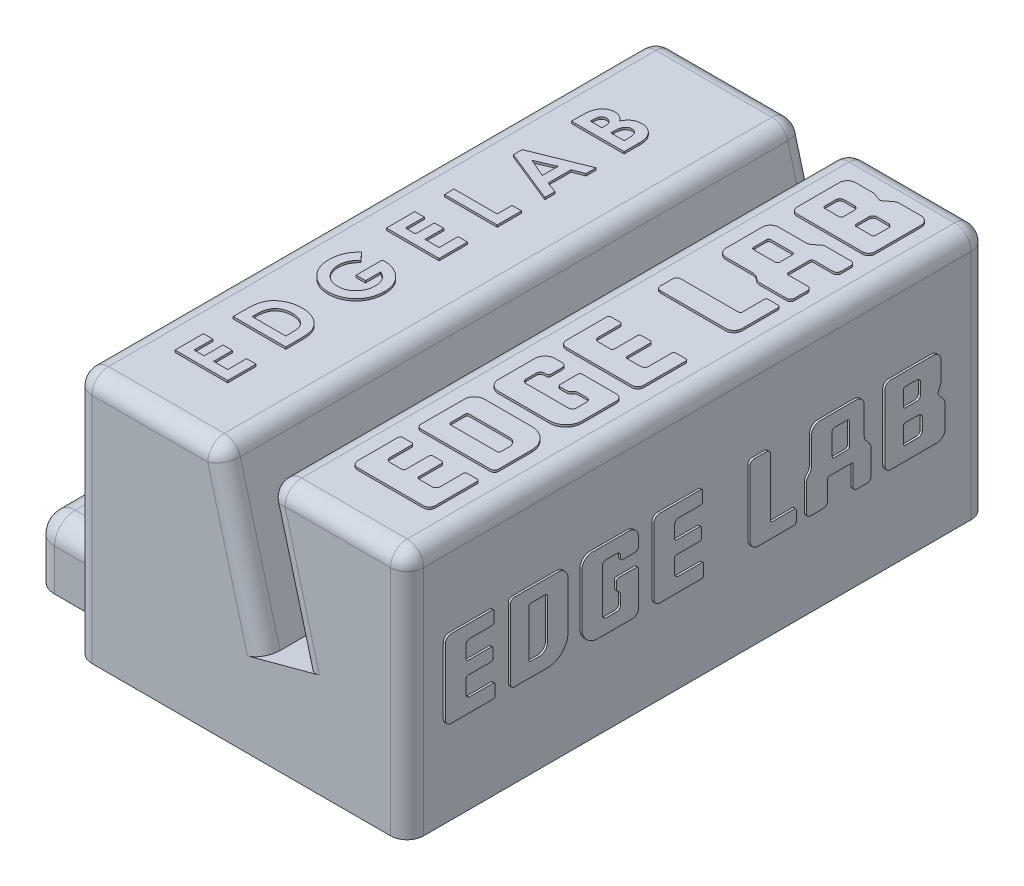
SolidWorks part; units mm, degrees
ref_plane "Front Plane" through (0, 0, 0) normal (0, 0, 1) x (1, 0, 0)
ref_plane "Top Plane" through (0, 0, 0) normal (0, 1, 0) x (1, 0, 0)
ref_plane "Right Plane" through (0, 0, 0) normal (1, 0, 0) x (0, 0, -1)
sketch "Sketch1" plane through (0, 0, 0) normal (0, 0, 1) x (1, 0, 0)
  line L0 (-5, 30) -> (5.3528, -8.637)
  line L1 (-40, -30) -> (40, -30)
  line L2 (-40, -30) -> (-40, 30)
  line L3 (-40, 30) -> (-5, 30)
  line L4 (40, -30) -> (40, 30)
  line L5 (-40, -30) -> (40, 30) construction
  line L6 (-40, 30) -> (40, -30) construction
  line L7 (5.3528, -8.637) -> (15.012, -6.0488)
  line L8 (15.012, -6.0488) -> (5.3528, 30)
  line L9 (5.3528, 30) -> (40, 30)
  point P0 (0, 0)
  dimension "D1" = 80
  dimension "D2" = 60
  dimension "D3" = 10
  dimension "D4" = 15
  dimension "D5" = 40
  dimension "D6" = 35
extrude "Boss-Extrude1" add sketch "Sketch1" along normal mid plane 140
fillet "Fillet1" radius 4 16 edges at (10.1824, 11.9756, 70) (0.1764, 10.6815, 70) (10.1824, 11.9756, -70) (0.1764, 10.6815, -70) (-40, 0, -70) (-40, 0, 70) (40, 0, 70) (40, 0, -70) (-22.5, 30, -70) (22.6764, 30, -70) (22.6764, 30, 70) (-22.5, 30, 70) (-40, 30, 0) (40, 30, 0) (5.3528, 30, 0) (-5, 30, 0)
sketch "Sketch2" plane through (0, 30, 0) normal (0, 1, 0) x (1, 0, 0)
  line L0 (-18.2056, -66) -> (-18.2056, 66) construction
  line L1 (-36, -66) -> (-8.0693, -66) construction
  line L2 (-4.2056, 66) -> (-4.2056, -66) construction
  line L3 (-8.0693, 66) -> (-36, 66) construction
  text T0 "<b>E D G E L A B </b>" font "Century Gothic" height in points 48
  dimension "D1" = 14
extrude "Boss-Extrude2" add sketch "Sketch2" along normal mid plane 1
sketch "Sketch3" plane through (40, 0, 0) normal (1, 0, 0) x (0, 0, -1)
  line L1 (-61.2851, 9.4066) -> (59.2413, 9.4066) construction
  line L2 (-61.2851, 9.4066) -> (-61.2851, -9.3242) construction
  line L3 (-61.2851, -9.3242) -> (59.2413, -9.3242) construction
  line L4 (59.2413, 9.4066) -> (59.2413, -9.3242) construction
  spline S0 degree 2 poles (49.1702, -1.7787) (49.1702, -3.634) (49.1702, -5.4894) (49.1702, -5.9794) (49.6602, -5.9794) (51.1939, -5.9794) (52.7277, -5.9794) (53.7077, -5.9794) (53.7077, -4.9994) knots -167.601718 -167.601718 -167.601718 -129.737239 -129.737239 -121.883257 -121.883257 -90.581831 -90.581831 -74.873868 -74.873868 -74.873868 weights 1 1 1 0.707107 1 1 1 0.707107 1
  spline S1 degree 2 poles (53.7077, -4.9994) (53.7077, -3.634) (53.7077, -2.2687) (53.7077, -1.2887) (52.7277, -1.2887) (51.1939, -1.2887) (49.6602, -1.2887) (49.1702, -1.2887) (49.1702, -1.7787) knots -250.329568 -250.329568 -250.329568 -222.465088 -222.465088 -206.757125 -206.757125 -175.4557 -175.4557 -167.601718 -167.601718 -167.601718 weights 1 1 1 0.707107 1 1 1 0.707107 1
  spline S2 degree 2 poles (53.3258, 2.7824) (53.3258, 4.0329) (53.3258, 5.2834) (53.3258, 6.2634) (52.3458, 6.2634) (51.003, 6.2634) (49.6602, 6.2634) (49.1702, 6.2634) (49.1702, 5.7734) knots 398.296758 398.296758 398.296758 423.817476 423.817476 439.525439 439.525439 466.92947 466.92947 474.783451 474.783451 474.783451 weights 1 1 1 0.707107 1 1 1 0.707107 1
  spline S3 degree 2 poles (49.1702, 5.7734) (49.1702, 4.0329) (49.1702, 2.2924) (49.1702, 1.8024) (49.6602, 1.8024) (51.003, 1.8024) (52.3458, 1.8024) (53.3258, 1.8024) (53.3258, 2.7824) knots 311.810065 311.810065 311.810065 347.330782 347.330782 355.184764 355.184764 382.588795 382.588795 398.296758 398.296758 398.296758 weights 1 1 1 0.707107 1 1 1 0.707107 1
  spline S4 degree 2 poles (44.6664, -7.8542) (44.6664, 0.0412) (44.6664, 7.9366) (44.6664, 9.4066) (46.1364, 9.4066) (51.2216, 9.4066) (56.3069, 9.4066) (58.2669, 9.4066) (58.2669, 7.4466) (58.2669, 5.3695) (58.2669, 3.2924) (58.2669, 2.9275) (58.1356, 2.5871) knots 461.80003 461.80003 461.80003 622.930523 622.930523 646.492467 646.492467 750.273029 750.273029 781.688955 781.688955 824.078534 824.078534 831.441149 831.441149 831.441149 weights 1 1 1 0.707107 1 1 1 0.707107 1 1 1 0.983108 1
  spline S5 degree 2 poles (58.1356, 2.5871) (57.8372, 1.8135) (57.5388, 1.04) (57.4394, 0.7821) (57.6086, 0.5636) (58.2197, -0.2255) (58.8308, -1.0145) (59.2413, -1.5444) (59.2413, -2.2147) (59.2413, -4.7894) (59.2413, -7.3642) (59.2413, -9.3242) (57.2813, -9.3242) (51.7088, -9.3242) (46.1364, -9.3242) (44.6664, -9.3242) (44.6664, -7.8542) knots 184.948682 184.948682 184.948682 201.869362 201.869362 207.005035 207.005035 227.373046 227.373046 240.553121 240.553121 293.098969 293.098969 324.514895 324.514895 438.238085 438.238085 461.80003 461.80003 461.80003 weights 1 1 1 0.870998 1 1 1 0.946204 1 1 1 0.707107 1 1 1 0.707107 1
  spline S6 degree 2 poles (35.651, 6.2634) (34.0595, 6.2634) (32.468, 6.2634) (31.978, 6.2634) (31.978, 5.7734) (31.978, 3.1282) (31.978, 0.483) (31.978, -0.007) (32.468, -0.007) knots -236.822202 -236.822202 -236.822202 -204.342778 -204.342778 -196.488797 -196.488797 -142.504795 -142.504795 -134.650813 -134.650813 -134.650813 weights 1 1 1 0.707107 1 1 1 0.707107 1
  spline S7 degree 2 poles (32.468, -0.007) (34.0595, -0.007) (35.651, -0.007) (36.141, -0.007) (36.141, 0.483) (36.141, 3.1282) (36.141, 5.7734) (36.141, 6.2634) (35.651, 6.2634) knots -338.993592 -338.993592 -338.993592 -306.514167 -306.514167 -298.660186 -298.660186 -244.676184 -244.676184 -236.822202 -236.822202 -236.822202 weights 1 1 1 0.707107 1 1 1 0.707107 1
  spline S8 degree 2 poles (39.7047, 7.4466) (39.7047, 9.4066) (37.7447, 9.4066) (33.3708, 9.4066) (28.9969, 9.4066) (27.0369, 9.4066) (27.0369, 7.4466) (27.0369, 4.1917) (27.0369, 0.9368) (27.0369, 0.2291) (26.5848, -0.3154) (26.4181, -0.5161) (26.2514, -0.7168) (25.7993, -1.2612) (25.7993, -1.9689) (25.7993, -5.1566) (25.7993, -8.3442) (25.7993, -9.3242) (26.7793, -9.3242) (28.3348, -9.3242) (29.8903, -9.3242) knots 400.035539 400.035539 400.035539 431.451465 431.451465 520.714602 520.714602 552.130529 552.130529 618.557077 618.557077 632.417382 632.417382 637.741813 637.741813 651.602118 651.602118 716.655463 716.655463 732.363426 732.363426 764.108188 764.108188 764.108188 weights 1 0.707107 1 1 1 0.707107 1 1 1 0.940565 1 1 1 0.940565 1 1 1 0.707107 1 1 1
  spline S9 degree 2 poles (29.8903, -9.3242) (30.8703, -9.3242) (30.8703, -8.3442) (30.8703, -6.04) (30.8703, -3.7358) (30.8703, -3.2458) (31.3603, -3.2458) (33.9435, -3.2458) (36.5268, -3.2458) (37.0168, -3.2458) (37.0168, -3.7358) (37.0168, -6.04) (37.0168, -8.3442) (37.0168, -9.3242) (37.9968, -9.3242) (39.1851, -9.3242) (40.3734, -9.3242) (41.3534, -9.3242) (41.3534, -8.3442) (41.3534, -5.3156) (41.3534, -2.2871) (41.3534, -1.7563) (41.0143, -1.348) (40.5856, -0.8317) (40.1568, -0.3154) (39.7047, 0.2291) (39.7047, 0.9368) (39.7047, 4.1917) (39.7047, 7.4466) knots 0 0 0 15.707963 15.707963 62.731742 62.731742 70.585723 70.585723 123.304654 123.304654 131.158636 131.158636 178.182414 178.182414 193.890378 193.890378 218.142207 218.142207 233.85017 233.85017 295.657088 295.657088 306.052316 306.052316 319.748686 319.748686 333.608991 333.608991 400.035539 400.035539 400.035539 weights 1 0.707107 1 1 1 0.707107 1 1 1 0.707107 1 1 1 0.707107 1 1 1 0.707107 1 1 1 0.940565 1 1 1 0.940565 1 1 1
  spline S10 degree 2 poles (23.354, -8.8342) (23.354, -9.3242) (22.864, -9.3242) (18.4989, -9.3242) (14.1338, -9.3242) (12.1738, -9.3242) (12.1738, -7.3642) (12.1738, 0.5312) (12.1738, 8.4266) knots 297.338 297.338 297.338 305.191981 305.191981 394.275598 394.275598 425.691525 425.691525 586.822018 586.822018 586.822018 weights 1 0.707107 1 1 1 0.707107 1 1 1
  spline S11 degree 2 poles (12.1738, 8.4266) (12.1738, 9.4066) (13.1538, 9.4066) (14.6443, 9.4066) (16.1349, 9.4066) (17.1149, 9.4066) (17.1149, 8.4266) (17.1149, 1.4982) (17.1149, -5.4302) (17.1149, -5.9202) (17.6049, -5.9202) (20.2344, -5.9202) (22.864, -5.9202) (23.354, -5.9202) (23.354, -6.4102) (23.354, -7.6222) (23.354, -8.8342) knots 0 0 0 15.707963 15.707963 46.127608 46.127608 61.835571 61.835571 203.231548 203.231548 211.085529 211.085529 264.749502 264.749502 272.603484 272.603484 297.338 297.338 297.338 weights 1 0.707107 1 1 1 0.707107 1 1 1 0.707107 1 1 1 0.707107 1 1 1
  spline S12 degree 2 poles (-19.5122, 0.9279) (-20.0022, 0.9279) (-20.0022, 0.4379) (-20.0022, -0.3545) (-20.0022, -1.1469) (-20.0022, -1.6264) (-19.6237, -1.9206) (-19.501, -2.016) (-19.3784, -2.1114) (-18.9998, -2.4056) (-18.9998, -2.8851) (-18.9998, -3.9327) (-18.9998, -4.9803) (-18.9998, -5.9603) (-19.9798, -5.9603) (-21.2079, -5.9603) (-22.436, -5.9603) (-23.416, -5.9603) (-23.416, -4.9803) (-23.416, 0.1062) (-23.416, 5.1926) (-23.416, 6.1726) (-22.436, 6.1726) (-21.2079, 6.1726) (-19.9798, 6.1726) (-18.9998, 6.1726) (-18.9998, 5.1926) (-18.9998, 4.9395) (-18.9998, 4.6865) (-18.9998, 4.1965) (-18.5098, 4.1965) (-17.0861, 4.1965) (-15.6623, 4.1965) (-14.6823, 4.1965) (-14.6823, 5.1765) (-14.6823, 6.0665) (-14.6823, 6.9566) (-14.6823, 9.4066) (-17.1323, 9.4066) (-20.2742, 9.4066) (-23.416, 9.4066) knots 562.622876 562.622876 562.622876 570.476858 570.476858 586.648376 586.648376 595.748248 595.748248 598.919425 598.919425 608.019297 608.019297 629.399219 629.399219 645.107182 645.107182 670.169937 670.169937 685.8779 685.8779 789.683176 789.683176 805.391139 805.391139 830.453894 830.453894 846.161857 846.161857 851.326609 851.326609 859.180591 859.180591 888.236751 888.236751 903.944714 903.944714 922.109466 922.109466 961.379374 961.379374 1025.498289 1025.498289 1025.498289 weights 1 0.707107 1 1 1 0.898264 1 1 1 0.898264 1 1 1 0.707107 1 1 1 0.707107 1 1 1 0.707107 1 1 1 0.707107 1 1 1 0.707107 1 1 1 0.707107 1 1 1 0.707107 1 1 1
  spline S13 degree 2 poles (-23.416, 9.4066) (-24.6615, 9.4066) (-25.9071, 9.4066) (-28.3571, 9.4066) (-28.3571, 6.9566) (-28.3571, 0.7762) (-28.3571, -5.4042) (-28.3571, -9.3242) (-24.4371, -9.3242) (-20.2947, -9.3242) (-16.1523, -9.3242) (-14.6823, -9.3242) (-14.6823, -7.8542) (-14.6823, -3.7081) (-14.6823, 0.4379) (-14.6823, 0.9279) (-15.1723, 0.9279) (-17.3423, 0.9279) (-19.5122, 0.9279) knots 64.118914 64.118914 64.118914 89.538559 89.538559 128.808467 128.808467 254.93896 254.93896 317.770813 317.770813 402.309372 402.309372 425.871317 425.871317 510.484221 510.484221 518.338202 518.338202 562.622876 562.622876 562.622876 weights 1 1 1 0.707107 1 1 1 0.707107 1 1 1 0.707107 1 1 1 0.707107 1 1 1
  spline S14 degree 2 poles (-40.6388, 6.1726) (-38.8795, 6.1726) (-37.1203, 6.1726) (-36.6303, 6.1726) (-36.6303, 5.6826) (-36.6303, 0.8418) (-36.6303, -3.9991) (-36.6303, -5.9567) (-38.5879, -5.9591) knots -217.757092 -217.757092 -217.757092 -181.853982 -181.853982 -174 -174 -75.207429 -75.207429 -43.815822 -43.815822 -43.815822 weights 1 1 1 0.707107 1 1 1 0.707537 1
  spline S15 degree 2 poles (-38.5879, -5.9591) (-39.6131, -5.9603) (-40.6382, -5.9615) (-40.8413, -5.9618) (-40.9851, -5.8182) (-41.1288, -5.6747) (-41.1288, -5.4715) (-41.1288, 0.1055) (-41.1288, 5.6826) (-41.1288, 6.1726) (-40.6388, 6.1726) knots -368.210498 -368.210498 -368.210498 -347.289133 -347.289133 -343.359103 -343.359103 -339.429072 -339.429072 -225.611074 -225.611074 -217.757092 -217.757092 -217.757092 weights 1 1 1 0.923763 1 0.923763 1 1 1 0.707107 1
  spline S16 degree 2 poles (-36.5892, -9.3242) (-31.6892, -9.3242) (-31.6892, -4.4242) (-31.6892, 1.2662) (-31.6892, 6.9566) (-31.6892, 9.4066) (-34.1392, 9.4066) (-39.3695, 9.4066) (-44.5999, 9.4066) knots 284.288819 284.288819 284.288819 362.828635 362.828635 478.959128 478.959128 518.229036 518.229036 624.971435 624.971435 624.971435 weights 1 0.707107 1 1 1 0.707107 1 1 1
  spline S17 degree 2 poles (-44.5999, 9.4066) (-45.5799, 9.4066) (-45.5799, 8.4266) (-45.5799, 0.0412) (-45.5799, -8.3442) (-45.5799, -9.3242) (-44.5999, -9.3242) (-40.5945, -9.3242) (-36.5892, -9.3242) knots 0 0 0 15.707963 15.707963 186.838456 186.838456 202.546419 202.546419 284.288819 284.288819 284.288819 weights 1 0.707107 1 1 1 0.707107 1 1 1
  spline S82 degree 2 poles (-61.2851, 7.9366) (-61.2851, 0.0412) (-61.2851, -7.8542) (-61.2851, -9.3242) (-59.8151, -9.3242) (-54.7806, -9.3242) (-49.7461, -9.3242) (-49.2561, -9.3242) (-49.2561, -8.8342) (-49.2561, -7.6518) (-49.2561, -6.4694) (-49.2561, -5.9794) (-49.7461, -5.9794) (-52.5266, -5.9794) (-55.3071, -5.9794) (-56.2871, -5.9794) (-56.2871, -4.9994) (-56.2871, -3.389) (-56.2871, -1.7787) (-56.2871, -1.2887) (-55.7971, -1.2887) knots 475.999021 475.999021 475.999021 637.129514 637.129514 660.691459 660.691459 763.436857 763.436857 771.290839 771.290839 795.421332 795.421332 803.275313 803.275313 860.020712 860.020712 875.728675 875.728675 908.593155 908.593155 916.447135 916.447135 916.447135 weights 1 1 1 0.707107 1 1 1 0.707107 1 1 1 0.707107 1 1 1 0.707107 1 1 1 0.707107 1
  spline S83 degree 2 poles (-55.7971, -1.2887) (-53.0207, -1.2887) (-50.2443, -1.2887) (-49.7543, -1.2887) (-49.7543, -0.7987) (-49.7543, 0.2569) (-49.7543, 1.3124) (-49.7543, 1.8024) (-50.2443, 1.8024) (-53.0207, 1.8024) (-55.7971, 1.8024) (-56.2871, 1.8024) (-56.2871, 2.2924) (-56.2871, 3.7425) (-56.2871, 5.1926) (-56.2871, 6.1726) (-55.3071, 6.1726) (-52.6611, 6.1726) (-50.0151, 6.1726) (-49.5251, 6.1726) (-49.5251, 6.6626) (-49.5251, 7.7896) (-49.5251, 8.9166) (-49.5251, 9.4066) (-50.0151, 9.4066) (-54.9151, 9.4066) (-59.8151, 9.4066) (-61.2851, 9.4066) (-61.2851, 7.9366) knots 55.999999 55.999999 55.999999 112.661842 112.661842 120.515824 120.515824 142.057243 142.057243 149.911225 149.911225 206.573067 206.573067 214.427049 214.427049 244.02115 244.02115 259.729113 259.729113 313.729113 313.729113 321.583095 321.583095 344.583095 344.583095 352.437076 352.437076 452.437076 452.437076 475.999021 475.999021 475.999021 weights 1 1 1 0.707107 1 1 1 0.707107 1 1 1 0.707107 1 1 1 0.707107 1 1 1 0.707107 1 1 1 0.707107 1 1 1 0.707107 1
  spline S84 degree 2 poles (-11.0111, 7.9366) (-11.0111, 0.0412) (-11.0111, -7.8542) (-11.0111, -9.3242) (-9.5411, -9.3242) (-4.5066, -9.3242) (0.5279, -9.3242) (1.0179, -9.3242) (1.0179, -8.8342) (1.0179, -7.6518) (1.0179, -6.4694) (1.0179, -5.9794) (0.5279, -5.9794) (-2.2526, -5.9794) (-5.0331, -5.9794) (-6.0131, -5.9794) (-6.0131, -4.9994) (-6.0131, -3.389) (-6.0131, -1.7787) (-6.0131, -1.2887) (-5.5231, -1.2887) knots 475.999021 475.999021 475.999021 637.129514 637.129514 660.691459 660.691459 763.436857 763.436857 771.290839 771.290839 795.421332 795.421332 803.275313 803.275313 860.020712 860.020712 875.728675 875.728675 908.593155 908.593155 916.447135 916.447135 916.447135 weights 1 1 1 0.707107 1 1 1 0.707107 1 1 1 0.707107 1 1 1 0.707107 1 1 1 0.707107 1
  spline S85 degree 2 poles (-5.5231, -1.2887) (-2.7467, -1.2887) (0.0297, -1.2887) (0.5197, -1.2887) (0.5197, -0.7987) (0.5197, 0.2569) (0.5197, 1.3124) (0.5197, 1.8024) (0.0297, 1.8024) (-2.7467, 1.8024) (-5.5231, 1.8024) (-6.0131, 1.8024) (-6.0131, 2.2924) (-6.0131, 3.7425) (-6.0131, 5.1926) (-6.0131, 6.1726) (-5.0331, 6.1726) (-2.3871, 6.1726) (0.2589, 6.1726) (0.7489, 6.1726) (0.7489, 6.6626) (0.7489, 7.7896) (0.7489, 8.9166) (0.7489, 9.4066) (0.2589, 9.4066) (-4.6411, 9.4066) (-9.5411, 9.4066) (-11.0111, 9.4066) (-11.0111, 7.9366) knots 55.999999 55.999999 55.999999 112.661842 112.661842 120.515824 120.515824 142.057243 142.057243 149.911225 149.911225 206.573067 206.573067 214.427049 214.427049 244.02115 244.02115 259.729113 259.729113 313.729113 313.729113 321.583095 321.583095 344.583095 344.583095 352.437076 352.437076 452.437076 452.437076 475.999021 475.999021 475.999021 weights 1 1 1 0.707107 1 1 1 0.707107 1 1 1 0.707107 1 1 1 0.707107 1 1 1 0.707107 1 1 1 0.707107 1 1 1 0.707107 1
extrude "Boss-Extrude3" add sketch "Sketch3" along normal mid plane 1
sketch "Sketch4" plane through (0, 30, 0) normal (0, 1, 0) x (1, 0, 0)
  line L1 (14.2135, -57.5951) -> (14.2135, 62.9313) construction
  line L2 (14.2135, -57.5951) -> (32.9443, -57.5951) construction
  line L3 (32.9443, -57.5951) -> (32.9443, 62.9313) construction
  line L4 (14.2135, 62.9313) -> (32.9443, 62.9313) construction
  spline S0 degree 2 poles (25.3988, 52.8602) (27.2541, 52.8602) (29.1095, 52.8602) (29.5995, 52.8602) (29.5995, 53.3502) (29.5995, 54.8839) (29.5995, 56.4177) (29.5995, 57.3977) (28.6195, 57.3977) knots -167.601718 -167.601718 -167.601718 -129.737239 -129.737239 -121.883257 -121.883257 -90.581831 -90.581831 -74.873868 -74.873868 -74.873868 weights 1 1 1 0.707107 1 1 1 0.707107 1
  spline S1 degree 2 poles (28.6195, 57.3977) (27.2541, 57.3977) (25.8888, 57.3977) (24.9088, 57.3977) (24.9088, 56.4177) (24.9088, 54.8839) (24.9088, 53.3502) (24.9088, 52.8602) (25.3988, 52.8602) knots -250.329568 -250.329568 -250.329568 -222.465088 -222.465088 -206.757125 -206.757125 -175.4557 -175.4557 -167.601718 -167.601718 -167.601718 weights 1 1 1 0.707107 1 1 1 0.707107 1
  spline S2 degree 2 poles (20.8377, 57.0158) (19.5872, 57.0158) (18.3367, 57.0158) (17.3567, 57.0158) (17.3567, 56.0358) (17.3567, 54.693) (17.3567, 53.3502) (17.3567, 52.8602) (17.8467, 52.8602) knots 398.296758 398.296758 398.296758 423.817476 423.817476 439.525439 439.525439 466.92947 466.92947 474.783451 474.783451 474.783451 weights 1 1 1 0.707107 1 1 1 0.707107 1
  spline S3 degree 2 poles (17.8467, 52.8602) (19.5872, 52.8602) (21.3277, 52.8602) (21.8177, 52.8602) (21.8177, 53.3502) (21.8177, 54.693) (21.8177, 56.0358) (21.8177, 57.0158) (20.8377, 57.0158) knots 311.810065 311.810065 311.810065 347.330782 347.330782 355.184764 355.184764 382.588795 382.588795 398.296758 398.296758 398.296758 weights 1 1 1 0.707107 1 1 1 0.707107 1
  spline S4 degree 2 poles (31.4743, 48.3564) (23.5789, 48.3564) (15.6835, 48.3564) (14.2135, 48.3564) (14.2135, 49.8264) (14.2135, 54.9116) (14.2135, 59.9969) (14.2135, 61.9569) (16.1735, 61.9569) (18.2506, 61.9569) (20.3277, 61.9569) (20.6926, 61.9569) (21.033, 61.8256) knots 461.80003 461.80003 461.80003 622.930523 622.930523 646.492467 646.492467 750.273029 750.273029 781.688955 781.688955 824.078534 824.078534 831.441149 831.441149 831.441149 weights 1 1 1 0.707107 1 1 1 0.707107 1 1 1 0.983108 1
  spline S5 degree 2 poles (21.033, 61.8256) (21.8066, 61.5272) (22.5801, 61.2288) (22.838, 61.1293) (23.0565, 61.2986) (23.8456, 61.9097) (24.6346, 62.5208) (25.1645, 62.9313) (25.8348, 62.9313) (28.4095, 62.9313) (30.9843, 62.9313) (32.9443, 62.9313) (32.9443, 60.9713) (32.9443, 55.3988) (32.9443, 49.8264) (32.9443, 48.3564) (31.4743, 48.3564) knots 184.948682 184.948682 184.948682 201.869362 201.869362 207.005035 207.005035 227.373046 227.373046 240.553121 240.553121 293.098969 293.098969 324.514895 324.514895 438.238085 438.238085 461.80003 461.80003 461.80003 weights 1 1 1 0.870998 1 1 1 0.946204 1 1 1 0.707107 1 1 1 0.707107 1
  spline S6 degree 2 poles (17.3567, 39.341) (17.3567, 37.7495) (17.3567, 36.158) (17.3567, 35.668) (17.8467, 35.668) (20.4919, 35.668) (23.1371, 35.668) (23.6271, 35.668) (23.6271, 36.158) knots -236.822202 -236.822202 -236.822202 -204.342778 -204.342778 -196.488797 -196.488797 -142.504795 -142.504795 -134.650813 -134.650813 -134.650813 weights 1 1 1 0.707107 1 1 1 0.707107 1
  spline S7 degree 2 poles (23.6271, 36.158) (23.6271, 37.7495) (23.6271, 39.341) (23.6271, 39.831) (23.1371, 39.831) (20.4919, 39.831) (17.8467, 39.831) (17.3567, 39.831) (17.3567, 39.341) knots -338.993592 -338.993592 -338.993592 -306.514167 -306.514167 -298.660186 -298.660186 -244.676184 -244.676184 -236.822202 -236.822202 -236.822202 weights 1 1 1 0.707107 1 1 1 0.707107 1
  spline S8 degree 2 poles (16.1735, 43.3947) (14.2135, 43.3947) (14.2135, 41.4347) (14.2135, 37.0608) (14.2135, 32.6869) (14.2135, 30.7269) (16.1735, 30.7269) (19.4284, 30.7269) (22.6833, 30.7269) (23.391, 30.7269) (23.9354, 30.2748) (24.1362, 30.1081) (24.3369, 29.9414) (24.8813, 29.4893) (25.589, 29.4893) (28.7766, 29.4893) (31.9643, 29.4893) (32.9443, 29.4893) (32.9443, 30.4693) (32.9443, 32.0248) (32.9443, 33.5803) knots 400.035539 400.035539 400.035539 431.451465 431.451465 520.714602 520.714602 552.130529 552.130529 618.557077 618.557077 632.417382 632.417382 637.741813 637.741813 651.602118 651.602118 716.655463 716.655463 732.363426 732.363426 764.108188 764.108188 764.108188 weights 1 0.707107 1 1 1 0.707107 1 1 1 0.940565 1 1 1 0.940565 1 1 1 0.707107 1 1 1
  spline S9 degree 2 poles (32.9443, 33.5803) (32.9443, 34.5603) (31.9643, 34.5603) (29.6601, 34.5603) (27.3559, 34.5603) (26.8659, 34.5603) (26.8659, 35.0503) (26.8659, 37.6335) (26.8659, 40.2167) (26.8659, 40.7067) (27.3559, 40.7067) (29.6601, 40.7067) (31.9643, 40.7067) (32.9443, 40.7067) (32.9443, 41.6867) (32.9443, 42.8751) (32.9443, 44.0634) (32.9443, 45.0434) (31.9643, 45.0434) (28.9357, 45.0434) (25.9072, 45.0434) (25.3764, 45.0434) (24.9681, 44.7043) (24.4517, 44.2756) (23.9354, 43.8468) (23.391, 43.3947) (22.6833, 43.3947) (19.4284, 43.3947) (16.1735, 43.3947) knots 0 0 0 15.707963 15.707963 62.731742 62.731742 70.585723 70.585723 123.304654 123.304654 131.158636 131.158636 178.182414 178.182414 193.890378 193.890378 218.142207 218.142207 233.85017 233.85017 295.657088 295.657088 306.052316 306.052316 319.748686 319.748686 333.608991 333.608991 400.035539 400.035539 400.035539 weights 1 0.707107 1 1 1 0.707107 1 1 1 0.707107 1 1 1 0.707107 1 1 1 0.707107 1 1 1 0.940565 1 1 1 0.940565 1 1 1
  spline S10 degree 2 poles (32.4543, 27.0439) (32.9443, 27.0439) (32.9443, 26.5539) (32.9443, 22.1888) (32.9443, 17.8238) (32.9443, 15.8638) (30.9843, 15.8638) (23.0889, 15.8638) (15.1935, 15.8638) knots 297.338 297.338 297.338 305.191981 305.191981 394.275598 394.275598 425.691525 425.691525 586.822018 586.822018 586.822018 weights 1 0.707107 1 1 1 0.707107 1 1 1
  spline S11 degree 2 poles (15.1935, 15.8638) (14.2135, 15.8638) (14.2135, 16.8438) (14.2135, 18.3343) (14.2135, 19.8249) (14.2135, 20.8049) (15.1935, 20.8049) (22.1219, 20.8049) (29.0503, 20.8049) (29.5403, 20.8049) (29.5403, 21.2949) (29.5403, 23.9244) (29.5403, 26.5539) (29.5403, 27.0439) (30.0303, 27.0439) (31.2423, 27.0439) (32.4543, 27.0439) knots 0 0 0 15.707963 15.707963 46.127608 46.127608 61.835571 61.835571 203.231548 203.231548 211.085529 211.085529 264.749502 264.749502 272.603484 272.603484 297.338 297.338 297.338 weights 1 0.707107 1 1 1 0.707107 1 1 1 0.707107 1 1 1 0.707107 1 1 1
  spline S12 degree 2 poles (22.6922, -15.8222) (22.6922, -16.3122) (23.1822, -16.3122) (23.9746, -16.3122) (24.767, -16.3122) (25.2464, -16.3122) (25.5407, -15.9337) (25.6361, -15.811) (25.7315, -15.6884) (26.0257, -15.3098) (26.5052, -15.3098) (27.5528, -15.3098) (28.6004, -15.3098) (29.5804, -15.3098) (29.5804, -16.2898) (29.5804, -17.5179) (29.5804, -18.746) (29.5804, -19.726) (28.6004, -19.726) (23.5139, -19.726) (18.4275, -19.726) (17.4475, -19.726) (17.4475, -18.746) (17.4475, -17.5179) (17.4475, -16.2898) (17.4475, -15.3098) (18.4275, -15.3098) (18.6805, -15.3098) (18.9336, -15.3098) (19.4236, -15.3098) (19.4236, -14.8198) (19.4236, -13.3961) (19.4236, -11.9723) (19.4236, -10.9923) (18.4436, -10.9923) (17.5535, -10.9923) (16.6635, -10.9923) (14.2135, -10.9923) (14.2135, -13.4423) (14.2135, -16.5842) (14.2135, -19.726) knots 562.622876 562.622876 562.622876 570.476858 570.476858 586.648376 586.648376 595.748248 595.748248 598.919425 598.919425 608.019297 608.019297 629.399219 629.399219 645.107182 645.107182 670.169937 670.169937 685.8779 685.8779 789.683176 789.683176 805.391139 805.391139 830.453894 830.453894 846.161857 846.161857 851.326609 851.326609 859.180591 859.180591 888.236751 888.236751 903.944714 903.944714 922.109466 922.109466 961.379374 961.379374 1025.498289 1025.498289 1025.498289 weights 1 0.707107 1 1 1 0.898264 1 1 1 0.898264 1 1 1 0.707107 1 1 1 0.707107 1 1 1 0.707107 1 1 1 0.707107 1 1 1 0.707107 1 1 1 0.707107 1 1 1 0.707107 1 1 1
  spline S13 degree 2 poles (14.2135, -19.726) (14.2135, -20.9716) (14.2135, -22.2171) (14.2135, -24.6671) (16.6635, -24.6671) (22.8439, -24.6671) (29.0243, -24.6671) (32.9443, -24.6671) (32.9443, -20.7471) (32.9443, -16.6047) (32.9443, -12.4623) (32.9443, -10.9923) (31.4743, -10.9923) (27.3282, -10.9923) (23.1822, -10.9923) (22.6922, -10.9923) (22.6922, -11.4823) (22.6922, -13.6523) (22.6922, -15.8222) knots 64.118914 64.118914 64.118914 89.538559 89.538559 128.808467 128.808467 254.93896 254.93896 317.770813 317.770813 402.309372 402.309372 425.871317 425.871317 510.484221 510.484221 518.338202 518.338202 562.622876 562.622876 562.622876 weights 1 1 1 0.707107 1 1 1 0.707107 1 1 1 0.707107 1 1 1 0.707107 1 1 1
  spline S14 degree 2 poles (17.4475, -36.9488) (17.4475, -35.1896) (17.4475, -33.4303) (17.4475, -32.9403) (17.9375, -32.9403) (22.7783, -32.9403) (27.6191, -32.9403) (29.5768, -32.9403) (29.5791, -34.8979) knots -217.757092 -217.757092 -217.757092 -181.853982 -181.853982 -174 -174 -75.207429 -75.207429 -43.815822 -43.815822 -43.815822 weights 1 1 1 0.707107 1 1 1 0.707537 1
  spline S15 degree 2 poles (29.5791, -34.8979) (29.5804, -35.9231) (29.5816, -36.9482) (29.5819, -37.1513) (29.4383, -37.2951) (29.2948, -37.4388) (29.0916, -37.4388) (23.5146, -37.4388) (17.9375, -37.4388) (17.4475, -37.4388) (17.4475, -36.9488) knots -368.210498 -368.210498 -368.210498 -347.289133 -347.289133 -343.359103 -343.359103 -339.429072 -339.429072 -225.611074 -225.611074 -217.757092 -217.757092 -217.757092 weights 1 1 1 0.923763 1 0.923763 1 1 1 0.707107 1
  spline S16 degree 2 poles (32.9443, -32.8992) (32.9443, -27.9992) (28.0443, -27.9992) (22.3539, -27.9992) (16.6635, -27.9992) (14.2135, -27.9992) (14.2135, -30.4492) (14.2135, -35.6796) (14.2135, -40.9099) knots 284.288819 284.288819 284.288819 362.828635 362.828635 478.959128 478.959128 518.229036 518.229036 624.971435 624.971435 624.971435 weights 1 0.707107 1 1 1 0.707107 1 1 1
  spline S17 degree 2 poles (14.2135, -40.9099) (14.2135, -41.8899) (15.1935, -41.8899) (23.5789, -41.8899) (31.9643, -41.8899) (32.9443, -41.8899) (32.9443, -40.9099) (32.9443, -36.9046) (32.9443, -32.8992) knots 0 0 0 15.707963 15.707963 186.838456 186.838456 202.546419 202.546419 284.288819 284.288819 284.288819 weights 1 0.707107 1 1 1 0.707107 1 1 1
  spline S82 degree 2 poles (15.6835, -57.5951) (23.5789, -57.5951) (31.4743, -57.5951) (32.9443, -57.5951) (32.9443, -56.1251) (32.9443, -51.0906) (32.9443, -46.0561) (32.9443, -45.5661) (32.4543, -45.5661) (31.2719, -45.5661) (30.0895, -45.5661) (29.5995, -45.5661) (29.5995, -46.0561) (29.5995, -48.8366) (29.5995, -51.6171) (29.5995, -52.5971) (28.6195, -52.5971) (27.0091, -52.5971) (25.3988, -52.5971) (24.9088, -52.5971) (24.9088, -52.1071) knots 475.999021 475.999021 475.999021 637.129514 637.129514 660.691459 660.691459 763.436857 763.436857 771.290839 771.290839 795.421332 795.421332 803.275313 803.275313 860.020712 860.020712 875.728675 875.728675 908.593155 908.593155 916.447135 916.447135 916.447135 weights 1 1 1 0.707107 1 1 1 0.707107 1 1 1 0.707107 1 1 1 0.707107 1 1 1 0.707107 1
  spline S83 degree 2 poles (24.9088, -52.1071) (24.9088, -49.3307) (24.9088, -46.5543) (24.9088, -46.0643) (24.4188, -46.0643) (23.3632, -46.0643) (22.3077, -46.0643) (21.8177, -46.0643) (21.8177, -46.5543) (21.8177, -49.3307) (21.8177, -52.1071) (21.8177, -52.5971) (21.3277, -52.5971) (19.8776, -52.5971) (18.4275, -52.5971) (17.4475, -52.5971) (17.4475, -51.6171) (17.4475, -48.9711) (17.4475, -46.3251) (17.4475, -45.8351) (16.9575, -45.8351) (15.8305, -45.8351) (14.7035, -45.8351) (14.2135, -45.8351) (14.2135, -46.3251) (14.2135, -51.2251) (14.2135, -56.1251) (14.2135, -57.5951) (15.6835, -57.5951) knots 55.999999 55.999999 55.999999 112.661842 112.661842 120.515824 120.515824 142.057243 142.057243 149.911225 149.911225 206.573067 206.573067 214.427049 214.427049 244.02115 244.02115 259.729113 259.729113 313.729113 313.729113 321.583095 321.583095 344.583095 344.583095 352.437076 352.437076 452.437076 452.437076 475.999021 475.999021 475.999021 weights 1 1 1 0.707107 1 1 1 0.707107 1 1 1 0.707107 1 1 1 0.707107 1 1 1 0.707107 1 1 1 0.707107 1 1 1 0.707107 1
  spline S84 degree 2 poles (15.6835, -7.3211) (23.5789, -7.3211) (31.4743, -7.3211) (32.9443, -7.3211) (32.9443, -5.8511) (32.9443, -0.8166) (32.9443, 4.2179) (32.9443, 4.7079) (32.4543, 4.7079) (31.2719, 4.7079) (30.0895, 4.7079) (29.5995, 4.7079) (29.5995, 4.2179) (29.5995, 1.4374) (29.5995, -1.3431) (29.5995, -2.3231) (28.6195, -2.3231) (27.0091, -2.3231) (25.3988, -2.3231) (24.9088, -2.3231) (24.9088, -1.8331) knots 475.999021 475.999021 475.999021 637.129514 637.129514 660.691459 660.691459 763.436857 763.436857 771.290839 771.290839 795.421332 795.421332 803.275313 803.275313 860.020712 860.020712 875.728675 875.728675 908.593155 908.593155 916.447135 916.447135 916.447135 weights 1 1 1 0.707107 1 1 1 0.707107 1 1 1 0.707107 1 1 1 0.707107 1 1 1 0.707107 1
  spline S85 degree 2 poles (24.9088, -1.8331) (24.9088, 0.9433) (24.9088, 3.7197) (24.9088, 4.2097) (24.4188, 4.2097) (23.3632, 4.2097) (22.3077, 4.2097) (21.8177, 4.2097) (21.8177, 3.7197) (21.8177, 0.9433) (21.8177, -1.8331) (21.8177, -2.3231) (21.3277, -2.3231) (19.8776, -2.3231) (18.4275, -2.3231) (17.4475, -2.3231) (17.4475, -1.3431) (17.4475, 1.3029) (17.4475, 3.9489) (17.4475, 4.4389) (16.9575, 4.4389) (15.8305, 4.4389) (14.7035, 4.4389) (14.2135, 4.4389) (14.2135, 3.9489) (14.2135, -0.9511) (14.2135, -5.8511) (14.2135, -7.3211) (15.6835, -7.3211) knots 55.999999 55.999999 55.999999 112.661842 112.661842 120.515824 120.515824 142.057243 142.057243 149.911225 149.911225 206.573067 206.573067 214.427049 214.427049 244.02115 244.02115 259.729113 259.729113 313.729113 313.729113 321.583095 321.583095 344.583095 344.583095 352.437076 352.437076 452.437076 452.437076 475.999021 475.999021 475.999021 weights 1 1 1 0.707107 1 1 1 0.707107 1 1 1 0.707107 1 1 1 0.707107 1 1 1 0.707107 1 1 1 0.707107 1 1 1 0.707107 1
extrude "Boss-Extrude4" add sketch "Sketch4" along normal mid plane 1
sketch "Sketch5" plane through (-40, 0, 0) normal (-1, 0, 0) x (0, 0, 1)
  line L0 (66, -30) -> (-66, -30) construction
  line L1 (-60, -30) -> (-40, -30)
  line L2 (-60, -30) -> (-60, -15)
  line L3 (-60, -15) -> (-40, -15)
  line L4 (-40, -30) -> (-40, -15)
  line L5 (0, 0) -> (0, -21.5725) construction
  line L6 (40, -30) -> (60, -30)
  line L7 (40, -30) -> (40, -15)
  line L8 (40, -15) -> (60, -15)
  line L9 (60, -30) -> (60, -15)
  dimension "D1" = 20
  dimension "D2" = 15
  dimension "D3" = 20
  dimension "D4" = 80
extrude "Boss-Extrude5" add sketch "Sketch5" along normal blind 20
fillet "Fillet3" radius 5 16 edges at (-60, -22.5, 40) (-60, -22.5, 60) (-40, -22.5, 40) (-40, -22.5, 60) (-60, -22.5, -60) (-40, -22.5, -60) (-40, -22.5, -40) (-60, -22.5, -40) (-60, -15, -50) (-40, -15, -50) (-50, -15, -60) (-50, -15, -40) (-50, -15, 60) (-60, -15, 50) (-50, -15, 40) (-40, -15, 50)
